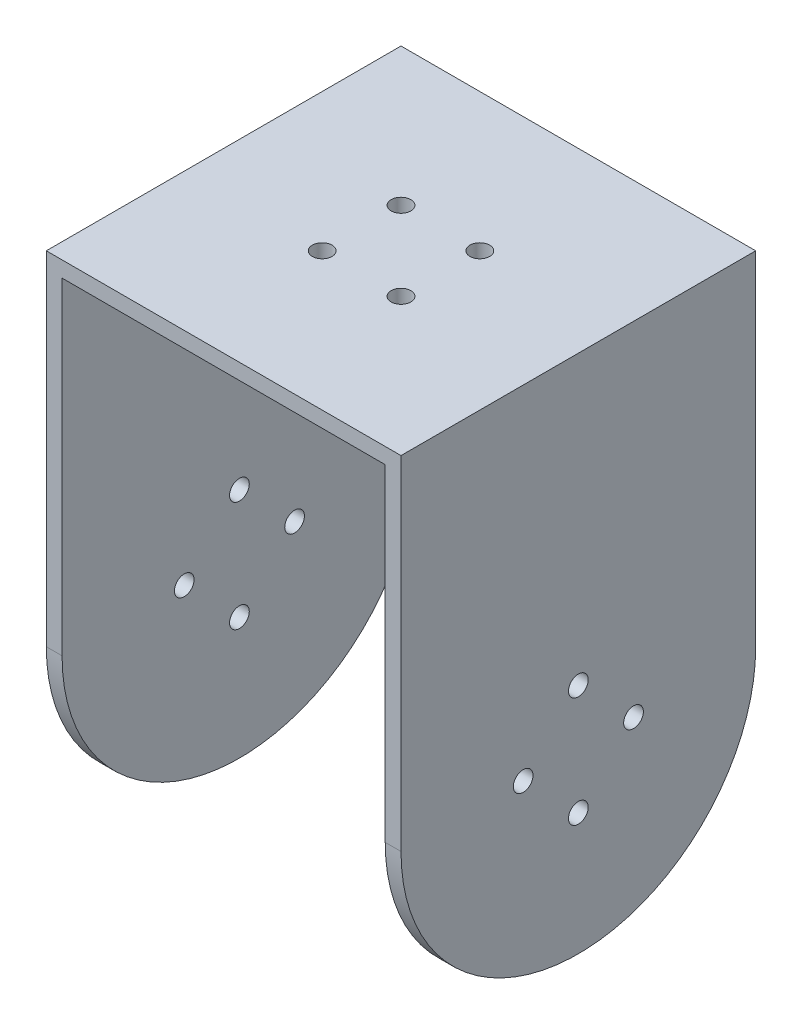
SolidWorks part; units mm, degrees
ref_plane "Front Plane" through (0, 0, 0) normal (0, 0, 1) x (1, 0, 0)
ref_plane "Top Plane" through (0, 0, 0) normal (0, 1, 0) x (1, 0, 0)
ref_plane "Right Plane" through (0, 0, 0) normal (1, 0, 0) x (0, 0, -1)
sketch "Sketch6" plane through (0, 0, 0) normal (1, 0, 0) x (0, 0, -1)
  line L3 (-22.5, 0) -> (-22.5, 43.5)
  line L4 (-22.5, 43.5) -> (22.5, 43.5)
  line L5 (22.5, 0) -> (22.5, 43.5)
  arc A0 (22.5, 0) -> (-22.5, 0) centre (0, 0) cw
  dimension "D1" = 45
  dimension "D2" = 22.5
  dimension "D3" = 43.5
extrude "Boss-Extrude2" add sketch "Sketch6" along normal blind 22.5 and the other way blind 22.5
sketch "Sketch7" plane through (0, 0, 0) normal (0, 1, 0) x (1, 0, 0)
  line L0 (-22.5, -22.5) -> (22.5, -22.5) construction
  line L1 (-20.5, 22.5) -> (20.5, 22.5)
  line L2 (-20.5, 22.5) -> (-20.5, -22.5)
  line L3 (-20.5, -22.5) -> (20.5, -22.5)
  line L4 (20.5, 22.5) -> (20.5, -22.5)
  line L5 (-20.5, 22.5) -> (20.5, -22.5) construction
  line L6 (-20.5, -22.5) -> (20.5, 22.5) construction
  point P0 (0, 0)
  dimension "D1" = 41
extrude "Cut-Extrude4" cut sketch "Sketch7" against normal blind 22.5 and the other way blind 41.5
sketch "Sketch8" plane through (0, 43.5, 0) normal (0, 1, 0) x (1, 0, 0)
  line L5 (-5, 5) -> (5, -5) construction
  line L6 (-5, -5) -> (5, 5) construction
  circle A0 centre (-5, 5) radius 1.25
  circle A1 centre (5, -5) radius 1.25
  circle A2 centre (5, 5) radius 1.25
  circle A3 centre (-5, -5) radius 1.25
  point P0 (0, 0)
  dimension "D1" = 10
  dimension "D2" = 10
extrude "Cut-Extrude5" cut sketch "Sketch8" against normal blind 18.5
sketch "Sketch9" plane through (-22.5, 0, 0) normal (-1, 0, 0) x (0, 0, 1)
  circle A0 centre (0, 7) radius 1.25
  circle A1 centre (0, -7) radius 1.25
  circle A2 centre (-7, 0) radius 1.25
  circle A3 centre (7, 0) radius 1.25
extrude "Cut-Extrude6" cut sketch "Sketch9" against normal blind 58.5
sketch "Sketch10" plane through (-22.5, 0, 0) normal (-1, 0, 0) x (0, 0, 1)
  circle A1 centre (0, 0) radius 3.1818
extrude "Cut-Extrude7" cut sketch "Sketch10" against normal blind 1
